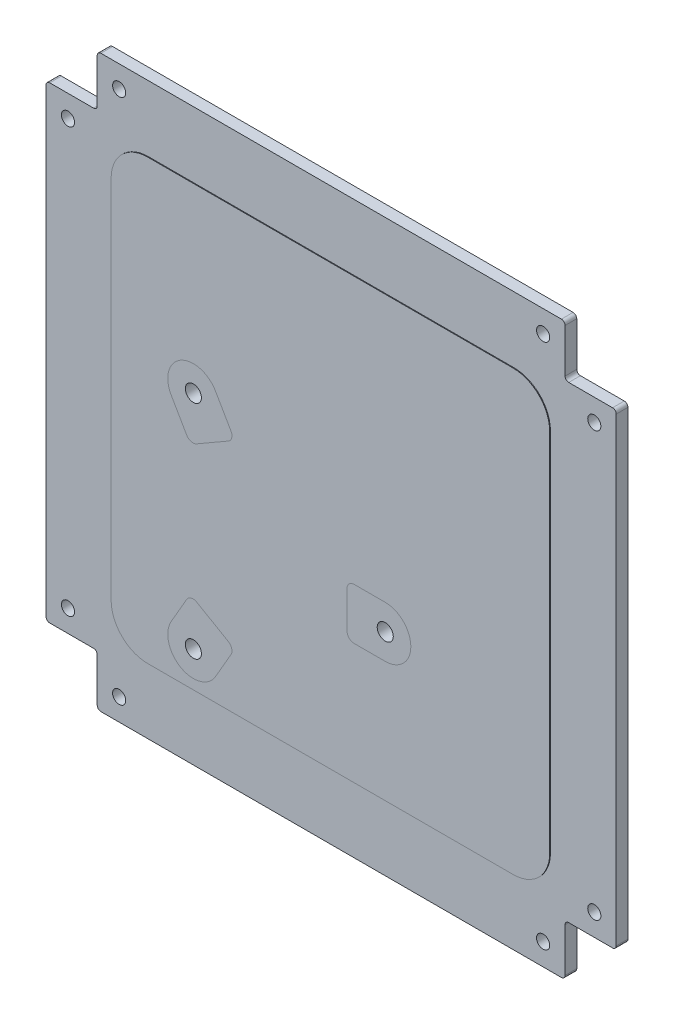
SolidWorks part; units mm, degrees
material "PET"
ref_plane "Front Plane" through (0, 0, 0) normal (0, 0, 1) x (1, 0, 0)
ref_plane "Top Plane" through (0, 0, 0) normal (0, 1, 0) x (1, 0, 0)
ref_plane "Right Plane" through (0, 0, 0) normal (1, 0, 0) x (0, 0, -1)
sketch "Sketch1" plane through (0, 0, 0) normal (0, 0, 1) x (1, 0, 0)
  line L0 (-32, 38.5) -> (-32, 32.5)
  line L1 (-31.5, -39) -> (31.5, -39)
  line L2 (-39, 31.5) -> (-39, -31.5)
  line L3 (-31.5, 39) -> (31.5, 39)
  line L4 (39, -31.5) -> (39, 31.5)
  line L5 (32, -38.5) -> (32, -32.5)
  line L6 (32.5, -32) -> (38.5, -32)
  line L7 (-32.5, 32) -> (-38.5, 32)
  line L8 (32, 38.5) -> (32, 32.5)
  line L9 (32.5, 32) -> (38.5, 32)
  line L10 (-38.5, -32) -> (-32.5, -32)
  line L11 (-32, -32.5) -> (-32, -38.5)
  line L12 (-32.5, -32.5) -> (32.5, 32.5) construction
  line L13 (32.5, -32.5) -> (-32.5, 32.5) construction
  arc A0 (-31.5, 39) -> (-32, 38.5) centre (-31.5, 38.5) ccw
  arc A1 (31.5, 39) -> (32, 38.5) centre (31.5, 38.5) cw
  arc A2 (32, 32.5) -> (32.5, 32) centre (32.5, 32.5) ccw
  arc A3 (38.5, 32) -> (39, 31.5) centre (38.5, 31.5) cw
  arc A4 (31.5, -39) -> (32, -38.5) centre (31.5, -38.5) ccw
  arc A5 (32.5, -32) -> (32, -32.5) centre (32.5, -32.5) ccw
  arc A6 (38.5, -32) -> (39, -31.5) centre (38.5, -31.5) ccw
  arc A7 (-32, -38.5) -> (-31.5, -39) centre (-31.5, -38.5) ccw
  arc A8 (-32, -32.5) -> (-32.5, -32) centre (-32.5, -32.5) ccw
  arc A9 (-39, -31.5) -> (-38.5, -32) centre (-38.5, -31.5) ccw
  arc A10 (-38.5, 32) -> (-39, 31.5) centre (-38.5, 31.5) ccw
  arc A11 (-32.5, 32) -> (-32, 32.5) centre (-32.5, 32.5) ccw
  point P0 (0, 0)
  dimension "D4" = 0.5
  dimension "D1" = 7
  dimension "D2" = 7
  dimension "D3" = 7
  dimension "D5" = 7
  dimension "D6" = 7
  dimension "D7" = 7
  dimension "D8" = 7
  dimension "D9" = 7
  dimension "D10" = 78
  dimension "D11" = 78
extrude "Boss-Extrude1" add sketch "Sketch1" along normal blind 1.6
sketch "Esboço1" plane through (0, 0, 1.6) normal (0, 0, 1) x (1, 0, 0)
  line L1 (-25, -30) -> (25, -30)
  line L2 (-30, -25) -> (-30, 25)
  line L3 (-25, 30) -> (25, 30)
  line L4 (30, -25) -> (30, 25)
  line L5 (-25, -25) -> (25, 25) construction
  line L6 (-25, 25) -> (25, -25) construction
  arc A0 (-30, 25) -> (-25, 30) centre (-25, 25) cw
  arc A1 (25, 30) -> (30, 25) centre (25, 25) cw
  arc A2 (30, -25) -> (25, -30) centre (25, -25) cw
  arc A3 (-25, -30) -> (-30, -25) centre (-25, -25) cw
  point P0 (0, 0)
  dimension "D1" = 5
  dimension "D2" = 60
  dimension "D3" = 60
extrude "Boss-Extrude2" add sketch "Esboço1" along normal blind 0.1
hole_wizard "M1.6 Hole1-FixingStructure" positions "Sketch3" profile "Sketch2" hole size "M1.6" standard "DIN"
sketch "Sketch3" plane through (0, 0, 0) normal (0, 0, -1) x (-1, 0, 0)
  line L0 (-31.5, 39) -> (31.5, 39) construction
  line L1 (31.5, -39) -> (-31.5, -39) construction
  line L2 (-39, -31.5) -> (-39, 31.5) construction
  line L3 (39, 31.5) -> (39, -31.5) construction
  line L4 (-31.5, 39) -> (31.5, 39) construction
  line L5 (31.5, -39) -> (-31.5, -39) construction
  line L6 (39, 31.5) -> (39, -31.5) construction
  line L7 (-39, -31.5) -> (-39, 31.5) construction
  point P0 (-29, 36)
  point P2 (29, 36)
  point P4 (-29, -36)
  point P6 (29, -36)
  point P20 (36, 29)
  point P22 (36, -29)
  point P24 (-36, -29)
  point P26 (-36, 29)
  dimension "D1" = 3
  dimension "D2" = 3
  dimension "D3" = 10
  dimension "D4" = 10
  dimension "D5" = 10
  dimension "D6" = 10
  dimension "D7" = 3
  dimension "D8" = 3
sketch "Sketch2" plane through (29, 36, 0) normal (1, 0, 0) x (0, 1, 0)
  line L0 (0, 0) -> (0, 200.5408)
  line L1 (0, 200.5408) -> (0.9, 200)
  line L2 (0.9, 200) -> (0.9, 0)
  line L5 (0.9, 0) -> (0, 0)
  line L10 (0, 200.5408) -> (-0.9, 200) construction
  line L11 (0, -6.35) -> (0, 107.95) construction
  dimension "Hole Dia." = 1.8
  dimension "Hole Depth" = 200
  dimension "Drill Angle" = 118
sketch "Sketch4" plane through (0, 0, 1.7) normal (0, 0, 1) x (1, 0, 0)
  circle A0 centre (-18.75, 5.1554) radius 1.1 construction
  circle A1 centre (-18.75, -25.1554) radius 1.1 construction
  circle A2 centre (7.5, -10) radius 1.1 construction
  circle A3 centre (-18.75, 5.1554) radius 1.1
  circle A4 centre (-18.75, -25.1554) radius 1.1
  circle A5 centre (7.5, -10) radius 1.1
extrude "Cut-Extrude1" cut sketch "Sketch4" against normal up to surface (1.7 mm away) up to face at (28.1, 36, 0)
sketch "Sketch7" plane through (0, 0, 1.7) normal (0, 0, 1) x (1, 0, 0)
  line L0 (-13.9682, -21.8731) -> (-18.2983, -19.3731) construction
  line L1 (-18.2983, -0.6269) -> (-13.9682, 1.8731)
  line L2 (-19.6643, -0.2609) -> (-21.7811, 3.4054)
  line L3 (-15.7189, 6.9054) -> (-13.6022, 3.2391)
  line L4 (-14.4682, -22.7391) -> (-18.7983, -20.2391) construction
  line L5 (-13.9682, -21.8731) -> (-18.2983, -19.3731)
  line L6 (-13.8564, -23.6795) -> (-15.7189, -26.9054)
  line L7 (-21.7811, -23.4054) -> (-19.9186, -20.1795)
  line L8 (-13.6022, -23.2391) -> (-15.7189, -26.9054)
  line L9 (-21.7811, -23.4054) -> (-19.6643, -19.7391)
  line L10 (-18.7983, 0.2391) -> (-14.4682, 2.7391) construction
  line L11 (2.2665, -7.5) -> (2.2665, -12.5)
  line L12 (3.2665, -6.5) -> (7.5, -6.5)
  line L13 (7.5, -13.5) -> (3.2665, -13.5)
  line L14 (3.2665, -7.5) -> (3.2665, -12.5) construction
  arc A0 (-13.6022, -23.2391) -> (-13.9682, -21.8731) centre (-14.4682, -22.7391) ccw
  arc A1 (-18.2983, -19.3731) -> (-19.6643, -19.7391) centre (-18.7983, -20.2391) ccw
  circle A2 centre (-10, -10) radius 10 construction
  arc A3 (-21.7811, -23.4054) -> (-15.7189, -26.9054) centre (-18.75, -25.1554) ccw
  arc A4 (-21.7811, -23.4054) -> (-15.7189, -26.9054) centre (-18.75, -25.1554) ccw
  arc A5 (-19.6643, -0.2609) -> (-18.2983, -0.6269) centre (-18.7983, 0.2391) ccw
  arc A6 (-13.9682, 1.8731) -> (-13.6022, 3.2391) centre (-14.4682, 2.7391) ccw
  arc A7 (-15.7189, 6.9054) -> (-21.7811, 3.4054) centre (-18.75, 5.1554) ccw
  arc A8 (3.2665, -6.5) -> (2.2665, -7.5) centre (3.2665, -7.5) ccw
  arc A9 (2.2665, -12.5) -> (3.2665, -13.5) centre (3.2665, -12.5) ccw
  arc A10 (7.5, -13.5) -> (7.5, -6.5) centre (7.5, -10) ccw
  point P17 (-10, -10)
  point P44 (-10, -10)
  dimension "D3" = 1
  dimension "D1" = 1
  dimension "D2" = 1
  dimension "D4" = 3
split line "Split Line1"
